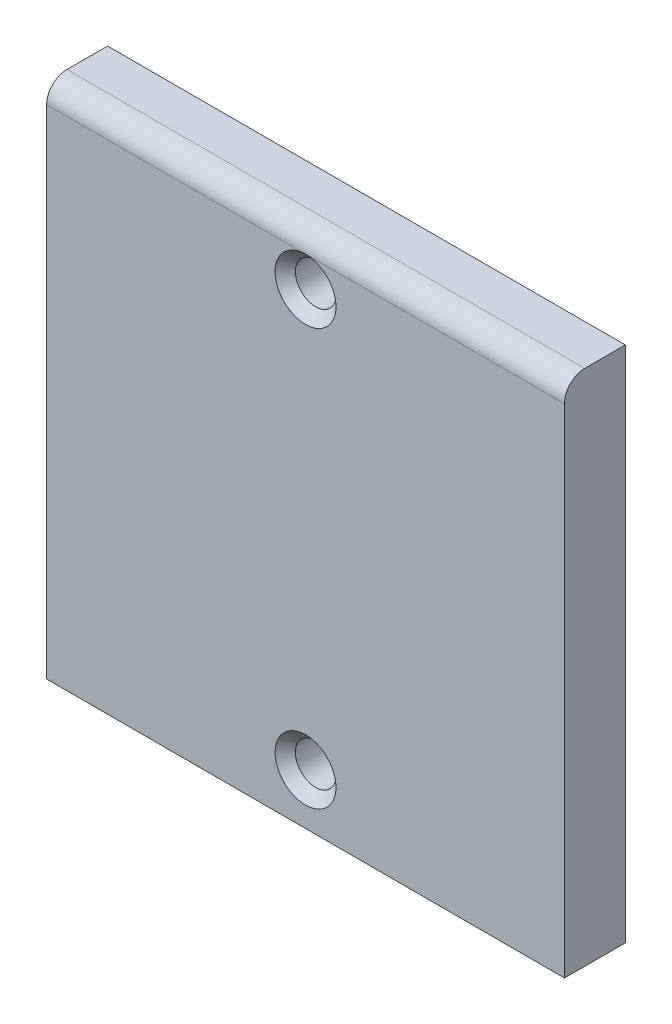
SolidWorks part; units mm, degrees
material "ABS"
ref_plane "Plano frontal" through (0, 0, 0) normal (0, 0, 1) x (1, 0, 0)
ref_plane "Plano superior" through (0, 0, 0) normal (0, 1, 0) x (1, 0, 0)
ref_plane "Plano direito" through (0, 0, 0) normal (1, 0, 0) x (0, 0, -1)
sketch "Esboço1" plane through (0, 0, 0) normal (0, 0, 1) x (1, 0, 0)
  line L1 (25.5, 25.5) -> (-25.5, 25.5)
  line L2 (25.5, 25.5) -> (25.5, -25.5)
  line L3 (25.5, -25.5) -> (-25.5, -25.5)
  line L4 (-25.5, 25.5) -> (-25.5, -25.5)
  line L5 (25.5, 25.5) -> (-25.5, -25.5) construction
  line L6 (25.5, -25.5) -> (-25.5, 25.5) construction
  point P0 (0, 0)
  dimension "D1" = 51
  dimension "D2" = 51
extrude "Ressalto-extrusão1" add sketch "Esboço1" along normal blind 6
sketch "Esboço2" plane through (0, 0, 0) normal (0, 0, -1) x (-1, 0, 0)
  line L0 (25.5, -25.5) -> (-25.5, -25.5) construction
  line L1 (-24.1, 12.4) -> (-17.6, 12.4)
  line L2 (-24.1, 12.4) -> (-24.1, -24.1)
  line L3 (-24.1, -24.1) -> (-17.6, -24.1)
  line L4 (-17.6, 12.4) -> (-17.6, -24.1)
  line L5 (-25.5, -25.5) -> (-25.5, 25.5) construction
  dimension "D1" = 6.5
  dimension "D2" = 36.5
  dimension "D3" = 1.4
  dimension "D4" = 1.4
extrude "Corte-extrusão1" cut sketch "Esboço2" against normal blind 4.5
sketch "Esboço3" plane through (0, 0, 6) normal (0, 0, 1) x (1, 0, 0)
  line L0 (25.5, 25.5) -> (-25.5, 25.5) construction
  line L1 (-25.5, -25.5) -> (25.5, -25.5) construction
  circle A0 centre (0, -20.5) radius 2
  circle A1 centre (0, 20.5) radius 2
  dimension "D1" = 4
  dimension "D2" = 5
  dimension "D3" = 5
extrude "Corte-extrusão2" cut sketch "Esboço3" against normal through all
sketch "Esboço4" plane through (0, 0, 0) normal (0, 0, -1) x (-1, 0, 0)
  line L1 (-14.7321, 17.5) -> (23.3328, -0.25)
  line L2 (-14.7321, 17.5) -> (-16, 14.7811)
  line L3 (-16, 14.7811) -> (22.0649, -2.9689)
  line L4 (23.3328, -0.25) -> (22.0649, -2.9689)
  line L6 (25.5, -25.5) -> (-25.5, -25.5) construction
  line L9 (-25.5, -25.5) -> (-25.5, 25.5) construction
  line L10 (-25.5, 25.5) -> (25.5, 25.5) construction
  point P4 (31.9937, -2.8131)
  point P5 (29.5909, -7.0181)
  point P7 (-15.9698, -21.1)
  point P8 (0, 0)
  point P9 (0, 0)
  point P10 (0, 0)
  point P11 (0, 0)
  point P14 (-14.8542, 20.6765)
  point P15 (0, 0)
  point P16 (-14.5, 5.6524)
  point P17 (21.3094, -13.3797)
  point P18 (21.191, -9.3539)
  point P20 (20.599, 1.5395)
  point P21 (18.8731, -9.9459)
  dimension "D1" = 3
  dimension "D2" = 25
  dimension "D3" = 42
  dimension "D4" = 9.5
  dimension "D5" = 8
extrude "Corte-extrusão3" cut sketch "Esboço4" against normal up to surface (4.5 mm away) up to face at (20.85, -5.85, 4.5)
pattern_linear "Padrão linear1" count 3 spacing 10 along (0, -1, 0) of "Corte-extrusão3"
fillet "Filete1" radius 2 1 edges at (0, 25.5, 6)
chamfer "Chanfro1" distance 1 angle 45 2 edges at (2, -20.5, 6) (2, 20.5, 6)
